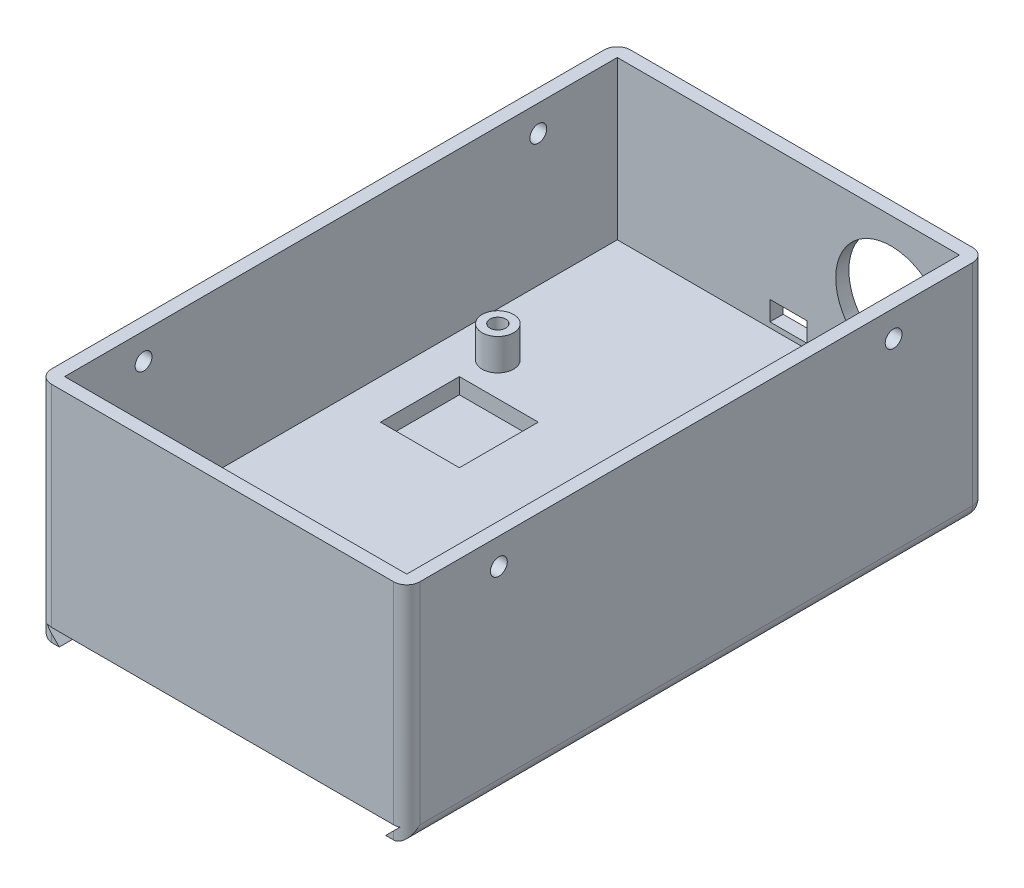
SolidWorks part; units mm, degrees
ref_plane "Front Plane" through (0, 0, 0) normal (0, 0, 1) x (1, 0, 0)
ref_plane "Top Plane" through (0, 0, 0) normal (0, 1, 0) x (1, 0, 0)
ref_plane "Right Plane" through (0, 0, 0) normal (1, 0, 0) x (0, 0, -1)
sketch "Sketch3" plane through (0, 0, 0) normal (0, 1, 0) x (1, 0, 0)
  line L1 (35, 55) -> (-35, 55)
  line L2 (35, 55) -> (35, -55)
  line L3 (35, -55) -> (-35, -55)
  line L4 (-35, 55) -> (-35, -55)
  line L5 (35, 55) -> (-35, -55) construction
  line L6 (35, -55) -> (-35, 55) construction
  point P0 (0, 0)
  dimension "D1" = 110
  dimension "D2" = 70
extrude "Boss-Extrude1" add sketch "Sketch3" along normal blind 3
sketch "Sketch4" plane through (0, 3, 0) normal (0, 1, 0) x (1, 0, 0)
  line L0 (35, -55) -> (35, 55) construction
  line L1 (-35, 55) -> (35, 55)
  line L2 (-35, 55) -> (-35, 52.5)
  line L3 (-35, 52.5) -> (35, 52.5)
  line L4 (35, 55) -> (35, 52.5)
  line L5 (-35, -55) -> (35, -55) construction
  line L6 (35, 52.5) -> (32.5, 52.5)
  line L7 (35, 52.5) -> (35, -55)
  line L8 (35, -55) -> (32.5, -55)
  line L9 (32.5, 52.5) -> (32.5, -55)
  line L10 (-35, 55) -> (-35, -55) construction
  line L11 (32.5, -55) -> (-35, -55)
  line L12 (32.5, -55) -> (32.5, -52.5)
  line L13 (32.5, -52.5) -> (-35, -52.5)
  line L14 (-35, -55) -> (-35, -52.5)
  line L16 (-35, -52.5) -> (-32.5, -52.5)
  line L17 (-35, -52.5) -> (-35, 52.5)
  line L18 (-35, 52.5) -> (-32.5, 52.5)
  line L19 (-32.5, -52.5) -> (-32.5, 52.5)
  line M9 (-35, 55) -> (-35, -55)
  line M10 (-35, -55) -> (35, -55)
  line M11 (35, -55) -> (35, 55)
  line M12 (35, 55) -> (-35, 55)
  dimension "D1" = 2.5
  dimension "D2" = 2.5
  dimension "D3" = 2.5
  dimension "D4" = 2.5
extrude "Boss-Extrude2" add sketch "Sketch4" along normal blind 30 contours L13 L19 L3 M9 | L3 M9 M11 M12 | L3 L9 M10 M11 | L9 L13 M9 M10
sketch "Sketch5" plane through (0, 3, 0) normal (0, 1, 0) x (1, 0, 0)
  line L1 (-28.5, 25.94) -> (27.89, 25.94)
  line L2 (-28.5, 25.94) -> (-28.5, -49.5)
  line L3 (-28.5, -49.5) -> (27.89, -49.5)
  line L4 (27.89, 25.94) -> (27.89, -49.5)
  line L5 (32.5, -52.5) -> (-32.5, -52.5) construction
  line L6 (-32.5, -52.5) -> (-32.5, 52.5) construction
  circle A0 centre (-24.06, 21.37) radius 3
  circle A1 centre (23.57, 21.37) radius 3
  circle A2 centre (-24.06, -45.31) radius 3
  circle A3 centre (23.57, -45.31) radius 3
  dimension "D9" = 6
  dimension "D10" = 6
  dimension "D11" = 6
  dimension "D12" = 6
  dimension "D2" = 56.39
  dimension "D3" = 4
  dimension "D4" = 75.44
  dimension "D5" = 4.44
  dimension "D6" = 4.32
  dimension "D7" = 4.57
  dimension "D8" = 4.19
  dimension "D13" = 3
extrude "Boss-Extrude3" add sketch "Sketch5" along normal blind 6 contours A0 | A1 | A3 | A2
sketch "Sketch7" plane through (0, 0, 0) normal (0, -1, 0) x (1, 0, 0)
  line L0 (-35, -55) -> (-35, 55) construction
  line L1 (35, 55) -> (-35, 55)
  line L2 (35, 55) -> (35, 52.5)
  line L3 (35, 52.5) -> (-35, 52.5)
  line L4 (-35, 55) -> (-35, 52.5)
  line L5 (35, -55) -> (-35, -55) construction
  line L6 (-35, 52.5) -> (-32.5, 52.5)
  line L7 (-35, 52.5) -> (-35, -55)
  line L8 (-35, -55) -> (-32.5, -55)
  line L9 (-32.5, 52.5) -> (-32.5, -55)
  line L10 (35, 55) -> (35, -55) construction
  line L11 (-32.5, -55) -> (35, -55)
  line L12 (-32.5, -55) -> (-32.5, -52.5)
  line L13 (-32.5, -52.5) -> (35, -52.5)
  line L14 (35, -55) -> (35, -52.5)
  line L16 (35, -52.5) -> (32.5, -52.5)
  line L17 (35, -52.5) -> (35, 52.5)
  line L18 (35, 52.5) -> (32.5, 52.5)
  line L19 (32.5, -52.5) -> (32.5, 52.5)
  line L20 (-32.5, -52.5) -> (32.5, -52.5)
  line L21 (-32.5, -52.5) -> (-32.5, 2.5)
  line L22 (-32.5, 2.5) -> (32.5, 2.5)
  line L23 (32.5, -52.5) -> (32.5, 2.5)
  line L24 (-32.5, 2.5) -> (32.5, 2.5)
  line L25 (-32.5, 2.5) -> (-32.5, 0)
  line L26 (-32.5, 0) -> (32.5, 0)
  line L27 (32.5, 2.5) -> (32.5, 0)
  line M9 (-35, 55) -> (-35, -55)
  line M10 (-35, -55) -> (35, -55)
  line M11 (35, -55) -> (35, 55)
  line M12 (35, 55) -> (-35, 55)
  dimension "D1" = 2.5
  dimension "D2" = 2.5
  dimension "D3" = 2.5
  dimension "D4" = 2.5
  dimension "D5" = 50
  dimension "D6" = 2.5
extrude "Boss-Extrude4" add sketch "Sketch7" along normal blind 9.5 contours L9 L3 L21 M9 M10 | L3 M11 M12 M9 | L19 L13 L3 L23 M11 | L13 L9 M10 M11 | L9 L26 L23 L22 | L17
sketch "Sketch8" plane through (0, 0, 2.5) normal (0, 0, 1) x (1, 0, 0)
  line L0 (-32.5, -9.5) -> (32.5, -9.5) construction
  line L1 (-32.5, 0) -> (0, 0)
  line L2 (-32.5, 0) -> (-32.5, -9.5)
  line L3 (-32.5, -9.5) -> (0, -9.5)
  line L4 (0, 0) -> (0, -9.5)
  line L6 (-10, 0) -> (-25, 0)
  line L7 (-10, 0) -> (-10, -6)
  line L8 (-10, -6) -> (-25, -6)
  line L9 (-25, 0) -> (-25, -6)
  line L14 (10, 0) -> (10, -6)
  line L15 (10, -6) -> (25, -6)
  line L16 (25, 0) -> (25, -6)
  line M1 (32.5, 0) -> (-32.5, 0)
  dimension "D1" = 10
  dimension "D3" = 15
  dimension "6" = 6
extrude "Cut-Extrude2" cut sketch "Sketch8" against normal up to surface (2.5 mm away) contours L16 L14 L15 M1 | L1 L9 L8 L7 up to face at (0, -4.75, 0)
sketch "Sketch9" plane through (0, 0, 0) normal (0, -1, 0) x (1, 0, 0)
  line L0 (32.5, -52.5) -> (32.5, 0) construction
  line L1 (-25, 0) -> (-10, 0)
  line L2 (-25, 0) -> (-25, -15)
  line L3 (-25, -15) -> (-10, -15)
  line L4 (-10, 0) -> (-10, -15)
  line L5 (10, 0) -> (25, 0)
  line L6 (10, 0) -> (10, -15)
  line L7 (10, -15) -> (25, -15)
  line L8 (25, 0) -> (25, -15)
  dimension "D1" = 15
  dimension "D2" = 15
  dimension "D3" = 22.5
extrude "Cut-Extrude3" cut sketch "Sketch9" against normal blind 3
sketch "Sketch10" plane through (0, 0, 0) normal (0, -1, 0) x (1, 0, 0)
  line L0 (-32.5, 2.5) -> (-25, 2.5) construction
  line L1 (-32.5, 52.5) -> (-31, 52.5)
  line L2 (-32.5, 52.5) -> (-32.5, 2.5)
  line L3 (-32.5, 2.5) -> (-31, 2.5)
  line L4 (-31, 52.5) -> (-31, 2.5)
  line L5 (32.5, 52.5) -> (-32.5, 52.5) construction
  line L10 (32.5, 2.5) -> (31, 2.5)
  line L11 (32.5, 2.5) -> (32.5, 52.5)
  line L12 (32.5, 52.5) -> (31, 52.5)
  line L13 (31, 2.5) -> (31, 52.5)
  dimension "D1" = 1.5
  dimension "D2" = 1.5
extrude "Boss-Extrude5" add sketch "Sketch10" along normal up to surface (9.5 mm away) up to face at (0, -9.5, 0)
sketch "Sketch11" plane through (0, 0, 55) normal (0, 0, 1) x (1, 0, 0)
  line L0 (31, -9.5) -> (33.5, -7)
  line L1 (-35, -9.5) -> (-31, -9.5)
  line L2 (-35, -9.5) -> (-35, -7)
  line L3 (-35, -7) -> (-31, -7)
  line L4 (-31, -9.5) -> (-31, -7)
  line L5 (0, 33) -> (0, -9.5) construction
  line L6 (-35, 33) -> (35, 33) construction
  line L7 (35, -9.5) -> (-35, -9.5) construction
  line L8 (35, -7) -> (31, -7)
  line L9 (31, -9.5) -> (31, -7)
  line L10 (-31, -7) -> (31, -7)
  line L11 (-31, -9.5) -> (-33.5, -7)
  line M9 (-35, -9.5) -> (35, -9.5)
  dimension "D1" = 4
  dimension "D2" = 2.5
  dimension "D4" = 2.5
extrude "Cut-Extrude5" cut sketch "Sketch11" against normal up to surface (52.5 mm away) contours L5 L10 L4 M9 | L11 L4 L3 | L10 L5 L9 M9 | L9 L0 L8 up to face at (0, -3.5833, 2.5)
sketch "Sketch12" plane through (0, 0, 0) normal (0, -1, 0) x (1, 0, 0)
  line L0 (31, 52.5) -> (-31, 52.5) construction
  line L1 (31, 52.5) -> (31, 2.5) construction
  circle A0 centre (0, 48) radius 3.5
  dimension "D1" = 7
  dimension "D2" = 4.5
  dimension "D3" = 31
extrude "Boss-Extrude6" add sketch "Sketch12" along normal up to surface (7 mm away) up to face at (0, -7, 28.125)
sketch "Sketch15" plane through (0, -7, 0) normal (0, -1, 0) x (1, 0, 0)
  circle A0 centre (0, 48) radius 1.5
  dimension "D1" = 3
extrude "Cut-Extrude6" cut sketch "Sketch15" against normal blind 6 contours A0
sketch "Sketch16" plane through (0, 0, -52.5) normal (0, 0, 1) x (1, 0, 0)
  line L0 (32.5, -9.5) -> (32.5, 0) construction
  line L1 (-32.5, -9.5) -> (32.5, -9.5)
  line L2 (-32.5, -9.5) -> (-32.5, -7)
  line L3 (-32.5, -7) -> (32.5, -7)
  line L4 (32.5, -9.5) -> (32.5, -7)
  dimension "D1" = 2.5
extrude "Boss-Extrude7" add sketch "Sketch16" along normal up to surface (52.5 mm away) up to face at (0, -3.5833, 0)
sketch "Sketch17" plane through (-35, 0, 0) normal (-1, 0, 0) x (0, 0, 1)
  line L0 (0, -9.5) -> (0, 33) construction
  line L1 (55, -9.5) -> (-55, -9.5) construction
  line L2 (-55, 33) -> (55, 33) construction
  line L3 (-55, 33) -> (-55, -9.5) construction
  circle A0 centre (-37.5, 28) radius 1.6
  circle A1 centre (37.5, 28) radius 1.6
  dimension "D1" = 3.2
  dimension "D2" = 5
  dimension "D3" = 17.5
extrude "Cut-Extrude7" cut sketch "Sketch17" against normal through all contours A0 | A1
sketch "Sketch18" plane through (0, 0, -55) normal (0, 0, -1) x (-1, 0, 0)
  line L0 (35, 33) -> (35, -9.5) construction
  line L1 (-3.5, 4) -> (3.5, 4)
  line L2 (-3.5, 4) -> (-3.5, 7.7)
  line L3 (-3.5, 7.7) -> (3.5, 7.7)
  line L4 (3.5, 4) -> (3.5, 7.7)
  line L5 (-3.5, 4) -> (3.5, 7.7) construction
  line L6 (-3.5, 7.7) -> (3.5, 4) construction
  line L7 (35, -9.5) -> (-35, -9.5) construction
  point P0 (0, 0)
  dimension "D1" = 7
  dimension "D2" = 3.7
  dimension "D3" = 13.5
  dimension "D4" = 31.5
extrude "Cut-Extrude8" cut sketch "Sketch18" against normal up to surface (2.5 mm away) contours L1 L4 L3 L2 up to face at (0, 18, -52.5)
sketch "Sketch19" plane through (0, 9, 0) normal (0, 1, 0) x (1, 0, 0)
  circle A0 centre (-24.06, -45.31) radius 1.5
  circle A1 centre (23.57, -45.31) radius 1.5
  circle A2 centre (23.57, 21.37) radius 1.5
  circle A3 centre (-24.06, 21.37) radius 1.5
  dimension "D1" = 3
  dimension "D2" = 3
  dimension "D3" = 3
  dimension "D4" = 3
extrude "Cut-Extrude9" cut sketch "Sketch19" against normal blind 6 contours A0 | A3 | A2 | A1
sketch "Sketch20" plane through (0, 0, -55) normal (0, 0, -1) x (-1, 0, 0)
  line L0 (-35, 33) -> (35, 33) construction
  line L1 (-35, 33) -> (-35, -9.5) construction
  circle A0 centre (-19.5, 17.5) radius 10.5
  dimension "D1" = 21
  dimension "D2" = 15.5
  dimension "D3" = 15.5
extrude "Cut-Extrude10" cut sketch "Sketch20" against normal up to surface (2.5 mm away) up to face at (0, 5.85, -52.5)
fillet "Fillet2" radius 2.5 4 edges at (35, 11.75, -55) (35, 11.75, 55) (-35, 11.75, -55) (-35, 11.75, 55)
fillet "Fillet3" radius 2.5 5 edges at (-34.2678, -9.5, -54.2678) (34.2678, -9.5, -54.2678) (35, -9.5, 0) (-35, -9.5, 0) (0, -9.5, -55)
